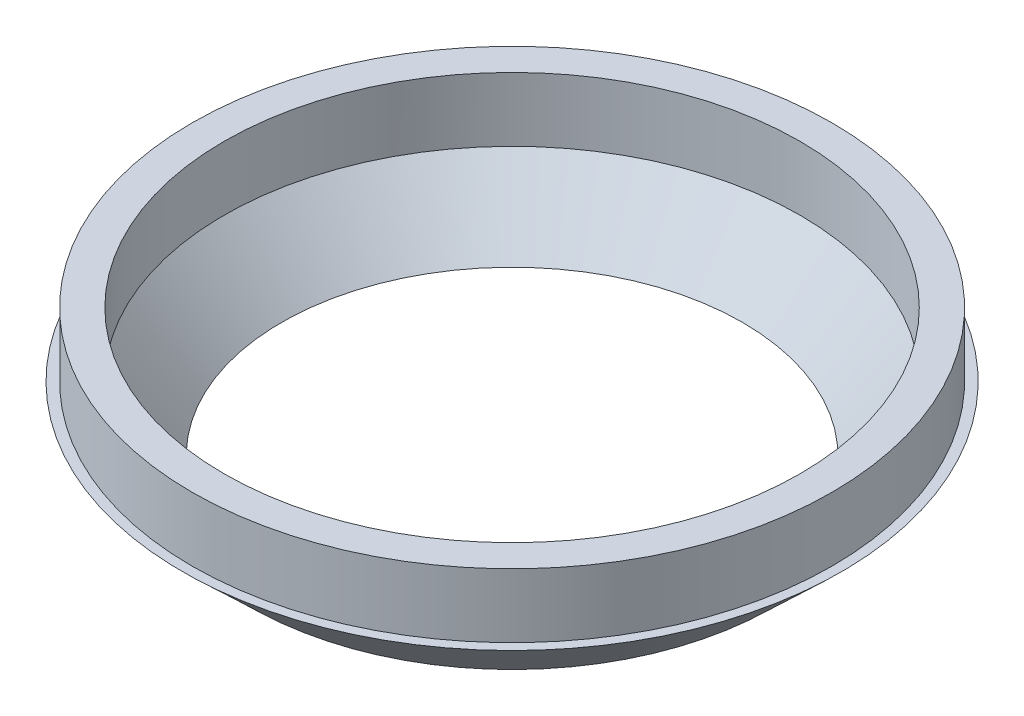
SolidWorks part; units mm, degrees
ref_plane "Front Plane" through (0, 0, 0) normal (0, 0, 1) x (1, 0, 0)
ref_plane "Top Plane" through (0, 0, 0) normal (0, 1, 0) x (1, 0, 0)
ref_plane "Right Plane" through (0, 0, 0) normal (1, 0, 0) x (0, 0, -1)
sketch "Sketch2" plane through (0, 0, 0) normal (0, 0, 1) x (1, 0, 0)
  line L0 (0, 0) -> (0, 12.7) construction
  line L1 (-45.72, 0) -> (-52.07, 0)
  line L2 (-57.15, 12.7) -> (-65.405, 12.7)
  line L3 (-65.405, 12.7) -> (-52.07, 0)
  line L4 (-57.15, 12.7) -> (-45.72, 0)
  dimension "D1" = 65.405
  dimension "D2" = 57.15
  dimension "D3" = 45.72
  dimension "D4" = 52.07
  dimension "D5" = 12.7
revolve "Revolve1" add sketch "Sketch2" angle 360 about L0
sketch "Sketch3" plane through (0, 12.7, 0) normal (0, 1, 0) x (1, 0, 0)
  circle A0 centre (0, 0) radius 57.15
  circle A1 centre (0, 0) radius 63.5
  dimension "D1" = 114.3
  dimension "D2" = 127
extrude "Boss-Extrude1" add sketch "Sketch3" along normal blind 12.7
equation "\"Inside Diamter\"= 5in"
equation "\"Inside Thickness\"= 0.5in"
equation "\"D2@Sketch2\"=(\"Inside Diamter\" - \"Inside Thickness\")/2"
equation "\"Bottom Diameter\"= 3.6"
equation "\"D3@Sketch2\" = \"Bottom Diameter\" / 2"
equation "\"D4@Sketch2\"= ( \"Bottom Diameter\" + \"Inside Thickness\" ) / 2"
equation "\"D1@Sketch3\"=\"Inside Diamter\"-\"Inside Thickness\""
equation "\"D2@Sketch3\"=\"Inside Diamter\""
